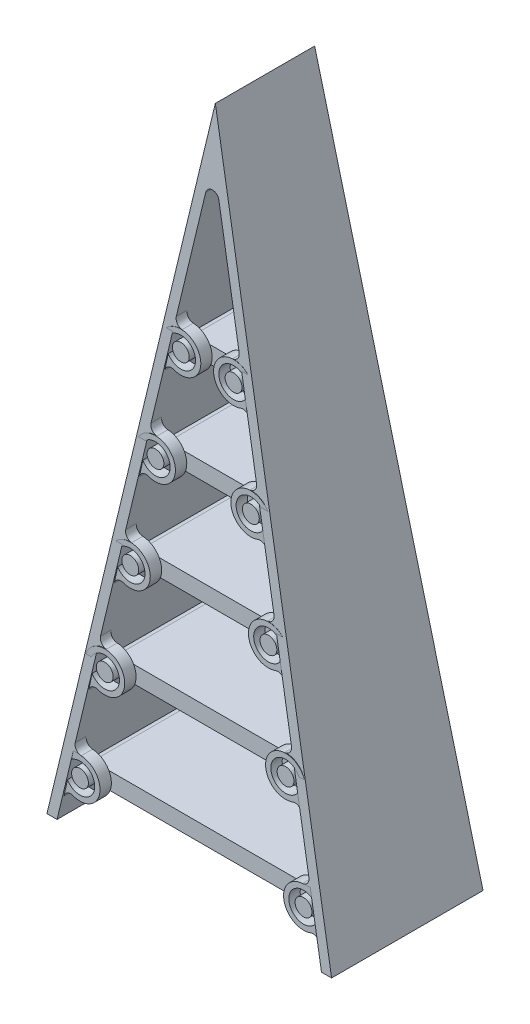
SolidWorks part; units mm, degrees
ref_plane "Ebene vorne" through (0, 0, 0) normal (0, 0, 1) x (1, 0, 0)
ref_plane "Ebene oben" through (0, 0, 0) normal (0, 1, 0) x (1, 0, 0)
ref_plane "Ebene rechts" through (0, 0, 0) normal (1, 0, 0) x (0, 0, -1)
ref_plane "Ebene7" through (0, 0, 9) normal (0, 0, 1) x (1, 0, 0)
sketch "Skizze1" plane through (0, 0, 0) normal (0, 0, 1) x (1, 0, 0)
  line L0 (0, 0) -> (16.9111, -80)
  line L1 (16.9111, -80) -> (15.7111, -80)
  line L2 (15.7111, -80) -> (0, -5.6767)
  line L3 (0, -5.6767) -> (-15.7111, -80)
  line L4 (-15.7111, -80) -> (-16.9111, -80)
  line L5 (-16.9111, -80) -> (0, 0)
  point P2 (-16.3111, -80)
  dimension "D1" = 1.2
  dimension "D2" = 1.2
  dimension "D3" = 23.872
  dimension "D4" = 80
extrude "Aufsatz-Linear austragen4" add sketch "Skizze1" along normal blind 18
ref_plane "Ebene8" through (17, 0, 0) normal (1, 0, 0) x (0, 0, -1)
sketch "Skizze11" plane through (17, 0, 0) normal (1, 0, 0) x (0, 0, -1)
  line L0 (-18, -80) -> (-14.9, 0)
  line L1 (-18, 0) -> (0, 0) construction
  line L2 (-14.9, 0) -> (-18, 0)
  line L3 (-18, 0) -> (-18, -80)
  line L4 (0, -80) -> (-3.1, 0)
  line L5 (-3.1, 0) -> (0, 0)
  line L6 (0, 0) -> (0, -80)
  dimension "D1" = 3.1
  dimension "D2" = 3.1
extrude "Schnitt-Linear austragen1" cut sketch "Skizze11" against normal through all
sketch "Skizze6" plane through (0, 0, 9) normal (0, 0, 1) x (1, 0, 0)
  line L1 (0, -5.6767) -> (-15.7111, -80) construction
  line L2 (15.7111, -80) -> (0, -5.6767) construction
  line L8 (3.1325, -25.6767) -> (-3.1325, -25.6767)
  line L11 (-3.1325, -27.6767) -> (3.1325, -27.6767)
  arc A0 (-3.1325, -25.6767) -> (-3.1325, -27.6767) centre (-3.1325, -26.6767) ccw
  arc A1 (3.1325, -25.6767) -> (3.1325, -27.6767) centre (3.1325, -26.6767) cw
  point P4 (-4.1325, -26.6767)
  point P9 (4.1325, -26.6767)
  dimension "D3" = 0.3
  dimension "D1" = 20
  dimension "D2" = 2
  dimension "D4" = 0.3
extrude "Aufsatz-Linear austragen5" add sketch "Skizze6" along normal blind 5.37 and the other way blind 5.37
sketch "Skizze7" plane through (0, 0, 9) normal (0, 0, 1) x (1, 0, 0)
  line L9 (5.6692, -37.6767) -> (-5.6692, -37.6767)
  line L12 (-5.6692, -39.6767) -> (5.6692, -39.6767)
  line L13 (-3.1325, -27.6767) -> (3.1325, -27.6767) construction
  line L14 (0, -5.6767) -> (-15.7111, -80) construction
  line L15 (15.7111, -80) -> (0, -5.6767) construction
  arc A0 (-5.6692, -37.6767) -> (-5.6692, -39.6767) centre (-5.6692, -38.6767) ccw
  arc A1 (5.6692, -37.6767) -> (5.6692, -39.6767) centre (5.6692, -38.6767) cw
  point P3 (-6.6692, -38.6767)
  point P10 (6.6692, -38.6767)
  dimension "D3" = 0.3
  dimension "D1" = 10
  dimension "D2" = 2
  dimension "D4" = 0.3
extrude "Aufsatz-Linear austragen6" add sketch "Skizze7" along normal blind 5.85 and the other way blind 5.85
sketch "Skizze8" plane through (0, 0, 9) normal (0, 0, 1) x (1, 0, 0)
  line L9 (8.2059, -49.6767) -> (-8.2059, -49.6767)
  line L12 (-8.2059, -51.6767) -> (8.2059, -51.6767)
  line L13 (-5.6692, -39.6767) -> (5.6692, -39.6767) construction
  line L14 (0, -5.6767) -> (-15.7111, -80) construction
  line L15 (15.7111, -80) -> (0, -5.6767) construction
  arc A0 (-8.2059, -49.6767) -> (-8.2059, -51.6767) centre (-8.2059, -50.6767) ccw
  arc A1 (8.2059, -49.6767) -> (8.2059, -51.6767) centre (8.2059, -50.6767) cw
  point P6 (-9.2059, -50.6767)
  point P11 (9.2059, -50.6767)
  dimension "D3" = 0.3
  dimension "D1" = 10
  dimension "D2" = 2
  dimension "D4" = 0.3
extrude "Aufsatz-Linear austragen7" add sketch "Skizze8" along normal blind 6.3 and the other way blind 6.3
sketch "Skizze9" plane through (0, 0, 9) normal (0, 0, 1) x (1, 0, 0)
  line L9 (10.7426, -61.6767) -> (-10.7426, -61.6767)
  line L12 (-10.7426, -63.6767) -> (10.7426, -63.6767)
  line L13 (-8.2059, -51.6767) -> (8.2059, -51.6767) construction
  line L14 (0, -5.6767) -> (-15.7111, -80) construction
  line L15 (15.7111, -80) -> (0, -5.6767) construction
  arc A0 (-10.7426, -61.6767) -> (-10.7426, -63.6767) centre (-10.7426, -62.6767) ccw
  arc A1 (10.7426, -61.6767) -> (10.7426, -63.6767) centre (10.7426, -62.6767) cw
  point P3 (-11.7426, -62.6767)
  point P10 (11.7426, -62.6767)
  dimension "D3" = 0.3
  dimension "D1" = 10
  dimension "D2" = 2
  dimension "D4" = 0.3
extrude "Aufsatz-Linear austragen8" add sketch "Skizze9" along normal blind 6.8 and the other way blind 6.8
sketch "Skizze10" plane through (0, 0, 9) normal (0, 0, 1) x (1, 0, 0)
  line L9 (13.2792, -73.6767) -> (-13.2792, -73.6767)
  line L12 (-13.2792, -75.6767) -> (13.2792, -75.6767)
  line L13 (-10.7426, -63.6767) -> (10.7426, -63.6767) construction
  line L14 (0, -5.6767) -> (-15.7111, -80) construction
  line L15 (15.7111, -80) -> (0, -5.6767) construction
  arc A0 (-13.2792, -73.6767) -> (-13.2792, -75.6767) centre (-13.2792, -74.6767) ccw
  arc A1 (13.2792, -73.6767) -> (13.2792, -75.6767) centre (13.2792, -74.6767) cw
  point P3 (-14.2792, -74.6767)
  point P10 (14.2792, -74.6767)
  dimension "D3" = 0.3
  dimension "D1" = 10
  dimension "D2" = 2
  dimension "D4" = 0.3
extrude "Aufsatz-Linear austragen9" add sketch "Skizze10" along normal blind 7.2 and the other way blind 7.2
sketch "Skizze13" plane through (0, 0, 14.37) normal (0, 0, 1) x (1, 0, 0)
  circle A0 centre (-3.1325, -26.6767) radius 1
  circle A1 centre (3.1325, -26.6767) radius 1
  dimension "D1" = 2
  dimension "D2" = 2
extrude "Aufsatz-Linear austragen12" add sketch "Skizze13" along normal blind 1.5
sketch "Skizze14" plane through (0, 0, 14.85) normal (0, 0, 1) x (1, 0, 0)
  circle A0 centre (-5.6692, -38.6767) radius 1
  circle A1 centre (5.6692, -38.6767) radius 1
extrude "Aufsatz-Linear austragen13" add sketch "Skizze14" along normal blind 1.5
sketch "Skizze15" plane through (0, 0, 15.3) normal (0, 0, 1) x (1, 0, 0)
  circle A0 centre (-8.2059, -50.6767) radius 1
  circle A1 centre (8.2059, -50.6767) radius 1
extrude "Aufsatz-Linear austragen14" add sketch "Skizze15" along normal blind 1.5
sketch "Skizze16" plane through (0, 0, 15.8) normal (0, 0, 1) x (1, 0, 0)
  circle A0 centre (-10.7426, -62.6767) radius 1
  circle A1 centre (10.7426, -62.6767) radius 1
extrude "Aufsatz-Linear austragen15" add sketch "Skizze16" along normal blind 1.5
sketch "Skizze17" plane through (0, 0, 16.2) normal (0, 0, 1) x (1, 0, 0)
  circle A0 centre (-13.2792, -74.6767) radius 1
  circle A1 centre (13.2792, -74.6767) radius 1
extrude "Aufsatz-Linear austragen16" add sketch "Skizze17" along normal blind 1.5
sketch "Skizze18" plane through (0, 0, 3.63) normal (0, 0, -1) x (-1, 0, 0)
  circle A0 centre (-3.1325, -26.6767) radius 1
  circle A1 centre (3.1325, -26.6767) radius 1
extrude "Aufsatz-Linear austragen17" add sketch "Skizze18" along normal blind 1.5
sketch "Skizze19" plane through (0, 0, 3.15) normal (0, 0, -1) x (-1, 0, 0)
  circle A0 centre (-5.6692, -38.6767) radius 1
  circle A1 centre (5.6692, -38.6767) radius 1
extrude "Aufsatz-Linear austragen18" add sketch "Skizze19" along normal blind 1.5
sketch "Skizze20" plane through (0, 0, 2.7) normal (0, 0, -1) x (-1, 0, 0)
  circle A0 centre (-8.2059, -50.6767) radius 1
  circle A1 centre (8.2059, -50.6767) radius 1
extrude "Aufsatz-Linear austragen19" add sketch "Skizze20" along normal blind 1.5
sketch "Skizze21" plane through (0, 0, 2.2) normal (0, 0, -1) x (-1, 0, 0)
  circle A0 centre (-10.7426, -62.6767) radius 1
  circle A1 centre (10.7426, -62.6767) radius 1
extrude "Aufsatz-Linear austragen20" add sketch "Skizze21" along normal blind 1.5
sketch "Skizze22" plane through (0, 0, 1.8) normal (0, 0, -1) x (-1, 0, 0)
  circle A0 centre (-13.2792, -74.6767) radius 1
  circle A1 centre (13.2792, -74.6767) radius 1
extrude "Aufsatz-Linear austragen21" add sketch "Skizze22" along normal blind 1.5
sketch "Skizze24" plane through (0, 0, 15.87) normal (0, 0, 1) x (1, 0, 0)
  circle A0 centre (-3.1325, -26.6767) radius 1.75
  circle A1 centre (-3.1325, -26.6767) radius 2.375
  circle A2 centre (3.1325, -26.6767) radius 1.75
  circle A3 centre (3.1325, -26.6767) radius 2.375
  dimension "D1" = 3.5
  dimension "D2" = 4.75
  dimension "D3" = 3.5
  dimension "D4" = 4.75
extrude "Aufsatz-Linear austragen22" add sketch "Skizze24" against normal blind 1.35
sketch "Skizze25" plane through (0, 0, 16.35) normal (0, 0, 1) x (1, 0, 0)
  circle A0 centre (-5.6692, -38.6767) radius 1.75
  circle A1 centre (-5.6692, -38.6767) radius 2.375
  circle A2 centre (5.6692, -38.6767) radius 1.75
  circle A3 centre (5.6692, -38.6767) radius 2.375
  dimension "D1" = 3.5
  dimension "D2" = 4.75
  dimension "D3" = 3.5
  dimension "D4" = 4.75
extrude "Aufsatz-Linear austragen23" add sketch "Skizze25" against normal blind 1.35
sketch "Skizze26" plane through (0, 0, 16.8) normal (0, 0, 1) x (1, 0, 0)
  circle A0 centre (-8.2059, -50.6767) radius 1.75
  circle A1 centre (-8.2059, -50.6767) radius 2.375
  circle A2 centre (8.2059, -50.6767) radius 1.75
  circle A3 centre (8.2059, -50.6767) radius 2.375
  dimension "D1" = 3.5
  dimension "D2" = 4.75
  dimension "D3" = 3.5
  dimension "D4" = 4.75
extrude "Aufsatz-Linear austragen24" add sketch "Skizze26" against normal blind 1.35
sketch "Skizze27" plane through (0, 0, 17.3) normal (0, 0, 1) x (1, 0, 0)
  circle A0 centre (-10.7426, -62.6767) radius 1.75
  circle A1 centre (-10.7426, -62.6767) radius 2.375
  circle A2 centre (10.7426, -62.6767) radius 1.75
  circle A3 centre (10.7426, -62.6767) radius 2.375
  dimension "D1" = 3.5
  dimension "D2" = 4.75
  dimension "D3" = 3.5
  dimension "D4" = 4.75
extrude "Aufsatz-Linear austragen25" add sketch "Skizze27" against normal blind 1.35
sketch "Skizze28" plane through (0, 0, 17.7) normal (0, 0, 1) x (1, 0, 0)
  circle A0 centre (-13.2792, -74.6767) radius 1.75
  circle A1 centre (-13.2792, -74.6767) radius 2.375
  circle A2 centre (13.2792, -74.6767) radius 1.75
  circle A3 centre (13.2792, -74.6767) radius 2.375
  dimension "D1" = 3.5
  dimension "D2" = 4.75
  dimension "D3" = 3.5
  dimension "D4" = 4.75
extrude "Aufsatz-Linear austragen26" add sketch "Skizze28" against normal blind 1.35
sketch "Skizze29" plane through (0, 0, 2.13) normal (0, 0, -1) x (-1, 0, 0)
  circle A0 centre (-3.1325, -26.6767) radius 1.75
  circle A1 centre (-3.1325, -26.6767) radius 2.375
  circle A2 centre (3.1325, -26.6767) radius 1.75
  circle A3 centre (3.1325, -26.6767) radius 2.375
extrude "Aufsatz-Linear austragen27" add sketch "Skizze29" against normal blind 1.35
sketch "Skizze30" plane through (0, 0, 1.65) normal (0, 0, -1) x (-1, 0, 0)
  circle A0 centre (-5.6692, -38.6767) radius 1.75
  circle A1 centre (-5.6692, -38.6767) radius 2.375
  circle A2 centre (5.6692, -38.6767) radius 1.75
  circle A3 centre (5.6692, -38.6767) radius 2.375
extrude "Aufsatz-Linear austragen28" add sketch "Skizze30" against normal blind 1.35
sketch "Skizze31" plane through (0, 0, 1.2) normal (0, 0, -1) x (-1, 0, 0)
  circle A0 centre (-8.2059, -50.6767) radius 1.75
  circle A1 centre (-8.2059, -50.6767) radius 2.375
  circle A2 centre (8.2059, -50.6767) radius 1.75
  circle A3 centre (8.2059, -50.6767) radius 2.375
extrude "Aufsatz-Linear austragen29" add sketch "Skizze31" against normal blind 1.35
sketch "Skizze32" plane through (0, 0, 0.7) normal (0, 0, -1) x (-1, 0, 0)
  circle A0 centre (-10.7426, -62.6767) radius 1.75
  circle A1 centre (-10.7426, -62.6767) radius 2.375
  circle A2 centre (10.7426, -62.6767) radius 1.75
  circle A3 centre (10.7426, -62.6767) radius 2.375
extrude "Aufsatz-Linear austragen30" add sketch "Skizze32" against normal blind 1.35
sketch "Skizze33" plane through (0, 0, 0.3) normal (0, 0, -1) x (-1, 0, 0)
  circle A0 centre (-13.2792, -74.6767) radius 1.75
  circle A1 centre (-13.2792, -74.6767) radius 2.375
  circle A2 centre (13.2792, -74.6767) radius 1.75
  circle A3 centre (13.2792, -74.6767) radius 2.375
extrude "Aufsatz-Linear austragen31" add sketch "Skizze33" against normal blind 1.35
fillet "Verrundung1" radius 0.8 1 edges at (0, -5.6767, 9)
fillet "Verrundung2" radius 0.8 40 edges at (12.4073, -64.3707, 16.625) (9.8706, -52.3707, 16.125) (7.3339, -40.3707, 15.675) (4.7973, -28.3707, 15.195) (-4.7973, -28.3707, 15.195) (-7.3339, -40.3707, 15.675) (-9.8706, -52.3707, 16.125) (-12.4073, -64.3707, 16.625) (-14.9439, -76.3707, 17.025) (14.9439, -76.3707, 17.025) (14.116, -72.454, 17.025) (-14.116, -72.454, 17.025) (-11.5793, -60.454, 16.5963) (11.5793, -60.454, 16.5963) (9.0427, -48.454, 16.1138) (-9.0427, -48.454, 16.1138) (-6.506, -36.454, 15.6563) (6.506, -36.454, 15.6563) (3.9693, -24.454, 15.1838) (-3.9693, -24.454, 15.1838) (-7.3339, -40.3707, 2.325) (-4.7973, -28.3707, 2.805) (-3.9693, -24.454, 2.8162) (-6.506, -36.454, 2.3437) (-9.0427, -48.454, 1.8862) (-9.8706, -52.3707, 1.875) (-12.4073, -64.3707, 1.375) (-11.5793, -60.454, 1.4037) (-14.116, -72.454, 0.975) (-14.9439, -76.3707, 0.975) (14.9439, -76.3707, 0.975) (14.116, -72.454, 0.975) (12.4073, -64.3707, 1.375) (11.5793, -60.454, 1.4037) (9.8706, -52.3707, 1.875) (9.0427, -48.454, 1.8862) (7.3339, -40.3707, 2.325) (6.506, -36.454, 2.3437) (4.7973, -28.3707, 2.805) (3.9693, -24.454, 2.8162)
